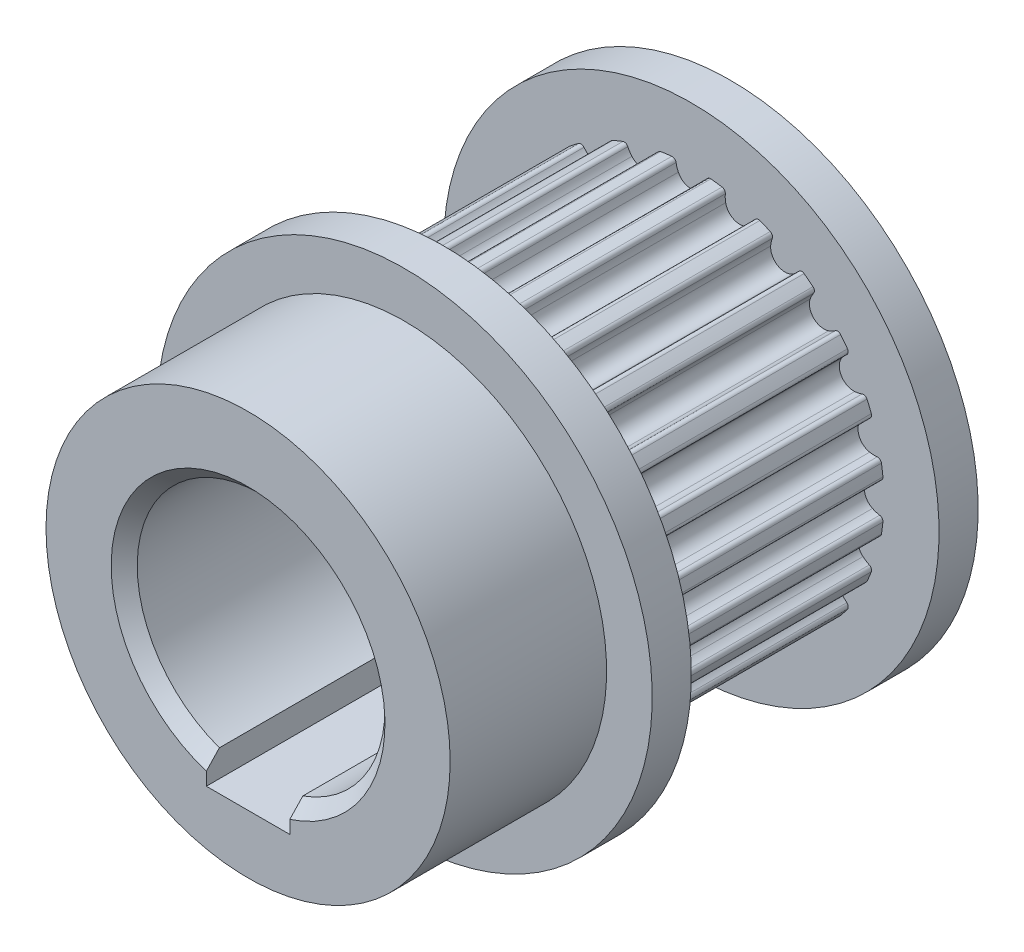
SolidWorks part; units mm, degrees
ref_plane "Front Plane" through (0, 0, 0) normal (0, 0, 1) x (1, 0, 0)
ref_plane "Top Plane" through (0, 0, 0) normal (0, 1, 0) x (1, 0, 0)
ref_plane "Right Plane" through (0, 0, 0) normal (1, 0, 0) x (0, 0, -1)
sketch "Sketch1" plane through (0, 0, 0) normal (0, 0, 1) x (1, 0, 0)
  line L0 (0, 7.6394) -> (0, -7.6394) construction
  line L1 (-7.6394, 0) -> (7.6394, 0) construction
  circle A0 centre (0, 0) radius 7.6394 construction
  circle A1 centre (0, 0) radius 8.0154 construction
  arc A2 (-0.7499, 7.3473) -> (0.7499, 7.3473) centre (0, 0) ccw
  circle A3 centre (0, 0) radius 6.6354 construction
  circle A4 centre (0, 7.1904) radius 0.555 construction
  circle A5 centre (0.4, 7.3854) radius 1 construction
  arc A6 (-0.5866, 7.2225) -> (-0.7499, 7.3473) centre (-0.7346, 7.198) ccw
  arc A7 (-0.5866, 7.2225) -> (-0.4989, 6.9472) centre (0.4, 7.3854) ccw
  arc A8 (-0.4989, 6.9472) -> (0.4989, 6.9472) centre (0, 7.1904) ccw
  arc A9 (0.5866, 7.2225) -> (0.4989, 6.9472) centre (-0.4, 7.3854) cw
  arc A10 (0.5866, 7.2225) -> (0.7499, 7.3473) centre (0.7346, 7.198) cw
  point P14 (-0.4989, 6.9472)
  dimension "D1" = 15.2789
  dimension "D2" = 1.38
  dimension "D3" = 0.75
  dimension "D4" = 0.254
  dimension "D5" = 2
  dimension "D6" = 1.11
  dimension "D8" = 0.3
  dimension "D7" = 0.4
extrude "Boss-Extrude1" add sketch "Sketch1" along normal blind 9.5
sketch "Sketch2" plane through (0, 0, 9.5) normal (0, 0, 1) x (1, 0, 0)
  arc A0 (-0.5866, 7.2225) -> (-0.7499, 7.3473) centre (-0.7346, 7.198) ccw construction
  arc A1 (-0.5866, 7.2225) -> (-0.4989, 6.9472) centre (0.4, 7.3854) ccw construction
  arc A2 (-0.4989, 6.9472) -> (0.4989, 6.9472) centre (0, 7.1904) ccw construction
  arc A3 (0.4989, 6.9472) -> (0.5866, 7.2225) centre (-0.4, 7.3854) ccw construction
  arc A4 (0.7499, 7.3473) -> (0.5866, 7.2225) centre (0.7346, 7.198) ccw construction
  arc A5 (-0.5866, 7.2225) -> (-0.7499, 7.3473) centre (-0.7346, 7.198) ccw
  arc A6 (-0.5866, 7.2225) -> (-0.4989, 6.9472) centre (0.4, 7.3854) ccw
  arc A7 (-0.4989, 6.9472) -> (0.4989, 6.9472) centre (0, 7.1904) ccw
  arc A8 (0.4989, 6.9472) -> (0.5866, 7.2225) centre (-0.4, 7.3854) ccw
  arc A9 (0.7499, 7.3473) -> (0.5866, 7.2225) centre (0.7346, 7.198) ccw
  arc A10 (1.3027, 7.1282) -> (1.1773, 7.291) centre (1.1534, 7.1429) ccw
  arc A11 (1.3027, 7.1282) -> (1.3162, 6.8396) centre (2.2979, 7.0303) ccw
  arc A12 (1.3162, 6.8396) -> (2.28, 6.5814) centre (1.861, 6.9454) ccw
  arc A13 (2.28, 6.5814) -> (2.436, 6.8246) centre (1.5251, 7.2373) ccw
  arc A14 (2.6259, 6.9028) -> (2.436, 6.8246) centre (2.5726, 6.7626) ccw
  arc A15 (3.1032, 6.5482) -> (3.0242, 6.7379) centre (2.9628, 6.601) ccw
  arc A16 (3.1032, 6.5482) -> (3.0416, 6.2659) centre (4.0391, 6.196) ccw
  arc A17 (3.0416, 6.2659) -> (3.9057, 5.767) centre (3.5952, 6.2271) ccw
  arc A18 (3.9057, 5.767) -> (4.1193, 5.9615) centre (3.3463, 6.596) ccw
  arc A19 (4.323, 5.988) -> (4.1193, 5.9615) centre (4.2352, 5.8664) ccw
  arc A20 (4.6923, 5.5219) -> (4.6651, 5.7255) centre (4.5703, 5.6092) ccw
  arc A21 (4.6923, 5.5219) -> (4.5597, 5.2652) centre (5.5051, 4.9394) ccw
  arc A22 (4.5597, 5.2652) -> (5.2652, 4.5597) centre (5.0844, 5.0844) ccw
  arc A23 (5.2652, 4.5597) -> (5.5219, 4.6923) centre (4.9394, 5.5051) ccw
  arc A24 (5.7255, 4.6651) -> (5.5219, 4.6923) centre (5.6092, 4.5703) ccw
  arc A25 (5.9615, 4.1193) -> (5.988, 4.323) centre (5.8664, 4.2352) ccw
  arc A26 (5.9615, 4.1193) -> (5.767, 3.9057) centre (6.596, 3.3463) ccw
  arc A27 (5.767, 3.9057) -> (6.2659, 3.0416) centre (6.2271, 3.5952) ccw
  arc A28 (6.2659, 3.0416) -> (6.5482, 3.1032) centre (6.196, 4.0391) ccw
  arc A29 (6.7379, 3.0242) -> (6.5482, 3.1032) centre (6.601, 2.9628) ccw
  arc A30 (6.8246, 2.436) -> (6.9028, 2.6259) centre (6.7626, 2.5726) ccw
  arc A31 (6.8246, 2.436) -> (6.5814, 2.28) centre (7.2373, 1.5251) ccw
  arc A32 (6.5814, 2.28) -> (6.8396, 1.3162) centre (6.9454, 1.861) ccw
  arc A33 (6.8396, 1.3162) -> (7.1282, 1.3027) centre (7.0303, 2.2979) ccw
  arc A34 (7.291, 1.1773) -> (7.1282, 1.3027) centre (7.1429, 1.1534) ccw
  arc A35 (7.2225, 0.5866) -> (7.3473, 0.7499) centre (7.198, 0.7346) ccw
  arc A36 (7.2225, 0.5866) -> (6.9472, 0.4989) centre (7.3854, -0.4) ccw
  arc A37 (6.9472, 0.4989) -> (6.9472, -0.4989) centre (7.1904, 0) ccw
  arc A38 (6.9472, -0.4989) -> (7.2225, -0.5866) centre (7.3854, 0.4) ccw
  arc A39 (7.3473, -0.7499) -> (7.2225, -0.5866) centre (7.198, -0.7346) ccw
  arc A40 (7.1282, -1.3027) -> (7.291, -1.1773) centre (7.1429, -1.1534) ccw
  arc A41 (7.1282, -1.3027) -> (6.8396, -1.3162) centre (7.0303, -2.2979) ccw
  arc A42 (6.8396, -1.3162) -> (6.5814, -2.28) centre (6.9454, -1.861) ccw
  arc A43 (6.5814, -2.28) -> (6.8246, -2.436) centre (7.2373, -1.5251) ccw
  arc A44 (6.9028, -2.6259) -> (6.8246, -2.436) centre (6.7626, -2.5726) ccw
  arc A45 (6.5482, -3.1032) -> (6.7379, -3.0242) centre (6.601, -2.9628) ccw
  arc A46 (6.5482, -3.1032) -> (6.2659, -3.0416) centre (6.196, -4.0391) ccw
  arc A47 (6.2659, -3.0416) -> (5.767, -3.9057) centre (6.2271, -3.5952) ccw
  arc A48 (5.767, -3.9057) -> (5.9615, -4.1193) centre (6.596, -3.3463) ccw
  arc A49 (5.988, -4.323) -> (5.9615, -4.1193) centre (5.8664, -4.2352) ccw
  arc A50 (5.5219, -4.6923) -> (5.7255, -4.6651) centre (5.6092, -4.5703) ccw
  arc A51 (5.5219, -4.6923) -> (5.2652, -4.5597) centre (4.9394, -5.5051) ccw
  arc A52 (5.2652, -4.5597) -> (4.5597, -5.2652) centre (5.0844, -5.0844) ccw
  arc A53 (4.5597, -5.2652) -> (4.6923, -5.5219) centre (5.5051, -4.9394) ccw
  arc A54 (4.6651, -5.7255) -> (4.6923, -5.5219) centre (4.5703, -5.6092) ccw
  arc A55 (4.1193, -5.9615) -> (4.323, -5.988) centre (4.2352, -5.8664) ccw
  arc A56 (4.1193, -5.9615) -> (3.9057, -5.767) centre (3.3463, -6.596) ccw
  arc A57 (3.9057, -5.767) -> (3.0416, -6.2659) centre (3.5952, -6.2271) ccw
  arc A58 (3.0416, -6.2659) -> (3.1032, -6.5482) centre (4.0391, -6.196) ccw
  arc A59 (3.0242, -6.7379) -> (3.1032, -6.5482) centre (2.9628, -6.601) ccw
  arc A60 (2.436, -6.8246) -> (2.6259, -6.9028) centre (2.5726, -6.7626) ccw
  arc A61 (2.436, -6.8246) -> (2.28, -6.5814) centre (1.5251, -7.2373) ccw
  arc A62 (2.28, -6.5814) -> (1.3162, -6.8396) centre (1.861, -6.9454) ccw
  arc A63 (1.3162, -6.8396) -> (1.3027, -7.1282) centre (2.2979, -7.0303) ccw
  arc A64 (1.1773, -7.291) -> (1.3027, -7.1282) centre (1.1534, -7.1429) ccw
  arc A65 (0.5866, -7.2225) -> (0.7499, -7.3473) centre (0.7346, -7.198) ccw
  arc A66 (0.5866, -7.2225) -> (0.4989, -6.9472) centre (-0.4, -7.3854) ccw
  arc A67 (0.4989, -6.9472) -> (-0.4989, -6.9472) centre (0, -7.1904) ccw
  arc A68 (-0.4989, -6.9472) -> (-0.5866, -7.2225) centre (0.4, -7.3854) ccw
  arc A69 (-0.7499, -7.3473) -> (-0.5866, -7.2225) centre (-0.7346, -7.198) ccw
  arc A70 (-1.3027, -7.1282) -> (-1.1773, -7.291) centre (-1.1534, -7.1429) ccw
  arc A71 (-1.3027, -7.1282) -> (-1.3162, -6.8396) centre (-2.2979, -7.0303) ccw
  arc A72 (-1.3162, -6.8396) -> (-2.28, -6.5814) centre (-1.861, -6.9454) ccw
  arc A73 (-2.28, -6.5814) -> (-2.436, -6.8246) centre (-1.5251, -7.2373) ccw
  arc A74 (-2.6259, -6.9028) -> (-2.436, -6.8246) centre (-2.5726, -6.7626) ccw
  arc A75 (-3.1032, -6.5482) -> (-3.0242, -6.7379) centre (-2.9628, -6.601) ccw
  arc A76 (-3.1032, -6.5482) -> (-3.0416, -6.2659) centre (-4.0391, -6.196) ccw
  arc A77 (-3.0416, -6.2659) -> (-3.9057, -5.767) centre (-3.5952, -6.2271) ccw
  arc A78 (-3.9057, -5.767) -> (-4.1193, -5.9615) centre (-3.3463, -6.596) ccw
  arc A79 (-4.323, -5.988) -> (-4.1193, -5.9615) centre (-4.2352, -5.8664) ccw
  arc A80 (-4.6923, -5.5219) -> (-4.6651, -5.7255) centre (-4.5703, -5.6092) ccw
  arc A81 (-4.6923, -5.5219) -> (-4.5597, -5.2652) centre (-5.5051, -4.9394) ccw
  arc A82 (-4.5597, -5.2652) -> (-5.2652, -4.5597) centre (-5.0844, -5.0844) ccw
  arc A83 (-5.2652, -4.5597) -> (-5.5219, -4.6923) centre (-4.9394, -5.5051) ccw
  arc A84 (-5.7255, -4.6651) -> (-5.5219, -4.6923) centre (-5.6092, -4.5703) ccw
  arc A85 (-5.9615, -4.1193) -> (-5.988, -4.323) centre (-5.8664, -4.2352) ccw
  arc A86 (-5.9615, -4.1193) -> (-5.767, -3.9057) centre (-6.596, -3.3463) ccw
  arc A87 (-5.767, -3.9057) -> (-6.2659, -3.0416) centre (-6.2271, -3.5952) ccw
  arc A88 (-6.2659, -3.0416) -> (-6.5482, -3.1032) centre (-6.196, -4.0391) ccw
  arc A89 (-6.7379, -3.0242) -> (-6.5482, -3.1032) centre (-6.601, -2.9628) ccw
  arc A90 (-6.8246, -2.436) -> (-6.9028, -2.6259) centre (-6.7626, -2.5726) ccw
  arc A91 (-6.8246, -2.436) -> (-6.5814, -2.28) centre (-7.2373, -1.5251) ccw
  arc A92 (-6.5814, -2.28) -> (-6.8396, -1.3162) centre (-6.9454, -1.861) ccw
  arc A93 (-6.8396, -1.3162) -> (-7.1282, -1.3027) centre (-7.0303, -2.2979) ccw
  arc A94 (-7.291, -1.1773) -> (-7.1282, -1.3027) centre (-7.1429, -1.1534) ccw
  arc A95 (-7.2225, -0.5866) -> (-7.3473, -0.7499) centre (-7.198, -0.7346) ccw
  arc A96 (-7.2225, -0.5866) -> (-6.9472, -0.4989) centre (-7.3854, 0.4) ccw
  arc A97 (-6.9472, -0.4989) -> (-6.9472, 0.4989) centre (-7.1904, 0) ccw
  arc A98 (-6.9472, 0.4989) -> (-7.2225, 0.5866) centre (-7.3854, -0.4) ccw
  arc A99 (-7.3473, 0.7499) -> (-7.2225, 0.5866) centre (-7.198, 0.7346) ccw
  arc A100 (-7.1282, 1.3027) -> (-7.291, 1.1773) centre (-7.1429, 1.1534) ccw
  arc A101 (-7.1282, 1.3027) -> (-6.8396, 1.3162) centre (-7.0303, 2.2979) ccw
  arc A102 (-6.8396, 1.3162) -> (-6.5814, 2.28) centre (-6.9454, 1.861) ccw
  arc A103 (-6.5814, 2.28) -> (-6.8246, 2.436) centre (-7.2373, 1.5251) ccw
  arc A104 (-6.9028, 2.6259) -> (-6.8246, 2.436) centre (-6.7626, 2.5726) ccw
  arc A105 (-6.5482, 3.1032) -> (-6.7379, 3.0242) centre (-6.601, 2.9628) ccw
  arc A106 (-6.5482, 3.1032) -> (-6.2659, 3.0416) centre (-6.196, 4.0391) ccw
  arc A107 (-6.2659, 3.0416) -> (-5.767, 3.9057) centre (-6.2271, 3.5952) ccw
  arc A108 (-5.767, 3.9057) -> (-5.9615, 4.1193) centre (-6.596, 3.3463) ccw
  arc A109 (-5.988, 4.323) -> (-5.9615, 4.1193) centre (-5.8664, 4.2352) ccw
  arc A110 (-5.5219, 4.6923) -> (-5.7255, 4.6651) centre (-5.6092, 4.5703) ccw
  arc A111 (-5.5219, 4.6923) -> (-5.2652, 4.5597) centre (-4.9394, 5.5051) ccw
  arc A112 (-5.2652, 4.5597) -> (-4.5597, 5.2652) centre (-5.0844, 5.0844) ccw
  arc A113 (-4.5597, 5.2652) -> (-4.6923, 5.5219) centre (-5.5051, 4.9394) ccw
  arc A114 (-4.6651, 5.7255) -> (-4.6923, 5.5219) centre (-4.5703, 5.6092) ccw
  arc A115 (-4.1193, 5.9615) -> (-4.323, 5.988) centre (-4.2352, 5.8664) ccw
  arc A116 (-4.1193, 5.9615) -> (-3.9057, 5.767) centre (-3.3463, 6.596) ccw
  arc A117 (-3.9057, 5.767) -> (-3.0416, 6.2659) centre (-3.5952, 6.2271) ccw
  arc A118 (-3.0416, 6.2659) -> (-3.1032, 6.5482) centre (-4.0391, 6.196) ccw
  arc A119 (-3.0242, 6.7379) -> (-3.1032, 6.5482) centre (-2.9628, 6.601) ccw
  arc A120 (-2.436, 6.8246) -> (-2.6259, 6.9028) centre (-2.5726, 6.7626) ccw
  arc A121 (-2.436, 6.8246) -> (-2.28, 6.5814) centre (-1.5251, 7.2373) ccw
  arc A122 (-2.28, 6.5814) -> (-1.3162, 6.8396) centre (-1.861, 6.9454) ccw
  arc A123 (-1.3162, 6.8396) -> (-1.3027, 7.1282) centre (-2.2979, 7.0303) ccw
  arc A124 (-1.1773, 7.291) -> (-1.3027, 7.1282) centre (-1.1534, 7.1429) ccw
  circle A125 centre (0, 0) radius 7.3854
  point P267 (0, 0)
  arc M5 (-0.7499, 7.3473) -> (0.7499, 7.3473) centre (0, 0) ccw
  dimension "D1" = 24
extrude "Cut-Extrude1" cut sketch "Sketch2" against normal blind 9.5 contours A124 A120 A121 A122 A123 M5 | A14 A10 A11 A12 A13 M5 | A19 A15 A16 A17 A18 M5 | A24 A20 A21 A22 A23 M5 | A29 A25 A26 A27 A28 M5 | A34 A30 A31 A32 A33 M5 | A39 A35 A36 A37 A38 M5 | A44 A40 A41 A42 A43 M5 | A49 A45 A46 A47 A48 M5 | A54 A50 A51 A52 A53 M5 | A59 A55 A56 A57 A58 M5 | A64 A60 A61 A62 A63 M5 | A69 A65 A66 A67 A68 M5 | A74 A70 A71 A72 A73 M5 | A79 A75 A76 A77 A78 M5 | A84 A80 A81 A82 A83 M5 | A89 A85 A86 A87 A88 M5 | A94 A90 A91 A92 A93 M5 | A99 A95 A96 A97 A98 M5 | A104 A100 A101 A102 A103 M5 | A109 A105 A106 A107 A108 M5 | A114 A110 A111 A112 A113 M5 | A119 A115 A116 A117 A118 M5 region at (-1.8279, 6.8217, 9.5) region at (1.8279, 6.8217, 9.5) region at (-3.5312, 6.1161, 9.5) region at (3.5312, 6.1161, 9.5) region at (-4.9938, 4.9938, 9.5) region at (4.9938, 4.9938, 9.5) region at (-6.1161, 3.5312, 9.5) region at (6.1161, 3.5312, 9.5) region at (-6.8217, 1.8279, 9.5) region at (6.8217, 1.8279, 9.5) region at (-7.0623, 0, 9.5) region at (7.0623, 0, 9.5) region at (-6.8217, -1.8279, 9.5) region at (6.8217, -1.8279, 9.5) region at (-6.1161, -3.5312, 9.5) region at (6.1161, -3.5312, 9.5) region at (-4.9938, -4.9938, 9.5) region at (4.9938, -4.9938, 9.5) region at (-3.5312, -6.1161, 9.5) region at (3.5312, -6.1161, 9.5) region at (-1.8279, -6.8217, 9.5) region at (1.8279, -6.8217, 9.5) region at (0, -7.0623, 9.5)
sketch "Sketch3" plane through (0, 0, 9.5) normal (0, 0, 1) x (1, 0, 0)
  arc A0 (-2.6259, 6.9028) -> (-4.323, 5.988) centre (0, 0) ccw
  arc A1 (-4.323, 5.988) -> (-4.6651, 5.7255) centre (0, 0) ccw construction
sketch "Sketch4" plane through (0, 0, 0) normal (0, 0, -1) x (-1, 0, 0)
  circle A0 centre (0, 0) radius 4.75
  dimension "D1" = 9.5
extrude "Cut-Extrude2" cut sketch "Sketch4" against normal through all
sketch "Sketch6" plane through (0, 0, 0) normal (0, 0, -1) x (-1, 0, 0)
  circle A0 centre (0, 0) radius 9.5
  circle A1 centre (0, 0) radius 4.75 construction
  circle A2 centre (0, 0) radius 4.75
  dimension "D1" = 19
extrude "Boss-Extrude2" add sketch "Sketch6" along normal blind 1.5
extrude "Boss-Extrude4" add sketch "Sketch6<3>" against normal blind 1.5 from vertex starting at point (3.0242, 6.7378, 9.5)
sketch "Sketch6<3>" plane through (0, 0, 0) normal (0, 0, -1) x (-1, 0, 0) same geometry as "Sketch6"
sketch "Sketch7" plane through (0, 0, 11) normal (0, 0, 1) x (1, 0, 0)
  circle A0 centre (0, 0) radius 4.75 construction
  circle A1 centre (0, 0) radius 4.75
  circle A4 centre (0, 0) radius 7.75
  dimension "D1" = 3
extrude "Boss-Extrude5" add sketch "Sketch7" along normal blind 6
sketch "Sketch9" plane through (0, 0, 17) normal (0, 0, 1) x (1, 0, 0)
  line L1 (-1.6, 0) -> (1.6, 0)
  line L2 (-1.6, 0) -> (-1.6, -5.5)
  line L3 (-1.6, -5.5) -> (1.6, -5.5)
  line L4 (1.6, 0) -> (1.6, -5.5)
  point P0 (0, 0)
  point P6 (0, 0)
  point P7 (1.4068, 0)
  dimension "D1" = 3.2
  dimension "D2" = 5.5
extrude "Cut-Extrude3" cut sketch "Sketch9" against normal through all
chamfer "Chamfer1" distance 0.5 angle 45 2 edges at (0, 4.75, -1.5) (0, 4.75, 17)
